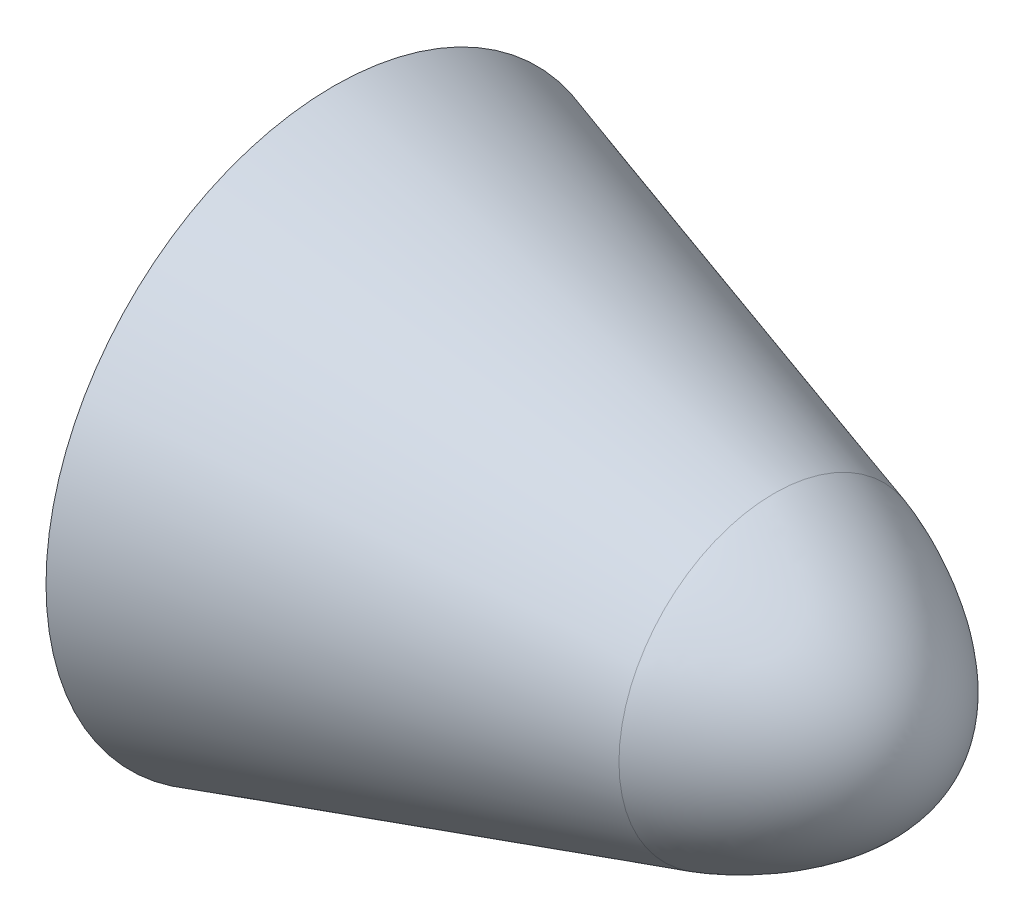
SolidWorks part; units mm, degrees
ref_plane "Front Plane" through (0, 0, 0) normal (0, 0, 1) x (1, 0, 0)
ref_plane "Top Plane" through (0, 0, 0) normal (0, 1, 0) x (1, 0, 0)
ref_plane "Right Plane" through (0, 0, 0) normal (1, 0, 0) x (0, 0, -1)
sketch "Sketch1" plane through (0, 0, 0) normal (0, 0, 1) x (1, 0, 0)
  line L0 (3563.2731, 697.1467) -> (3951.7533, 580.2767)
  line L1 (3563.2731, 443.4943) -> (4092.3062, 443.4943) construction
  line L3 (4092.3062, 503.058) -> (4092.3062, 383.9306) construction
  line L4 (3563.2731, 697.1467) -> (3563.2731, 443.4943)
  line L5 (3563.2731, 443.4943) -> (4092.3062, 443.4943)
  spline S0 degree 3 poles (4092.3062, 443.4943) (4092.3062, 523.6595) (3981.1101, 571.445) (3951.7533, 580.2767) knots 0 0 0 0 1 1 1 1
revolve "Revolve1" add sketch "Sketch1" angle 360 about L5
sketch "Sketch3" plane through (0, 0, 0) normal (0, 0, 1) x (1, 0, 0)
  line L0 (3563.2731, 443.4943) -> (4092.3062, 443.4943) construction
  line L1 (3563.2731, 697.1467) -> (3563.2731, 189.8418) construction
  ellipse E0 centre (3663.2731, 443.4943) end of major axis (3663.2731, 368.4943) minor radius 50
  dimension "D1" = 100
  dimension "D2" = 150
  dimension "D3" = 100
ref_plane "Plane1" through (0, -201.787, 770.6745) normal (0, 0.9144, -0.4048) x (1, 0, 0)
sketch "Sketch4" plane through (0, -201.787, 770.6745) normal (0, 0.9144, -0.4048) x (1, 0, 0)
  line L0 (3563.2731, 443.4943) -> (4092.3062, 443.4943) construction
  line L1 (3719.8416, 500.0628) -> (3606.7045, 386.9257) construction
  ellipse E0 centre (3663.2731, 443.4943) end of major axis (3606.7045, 386.9257) minor radius 16
  dimension "D1" = 32
  dimension "D2" = 160
  dimension "D3" = 45
ref_axis "Axis1" through (3563.2731, 443.4943, 0) along (1, 0, 0)
